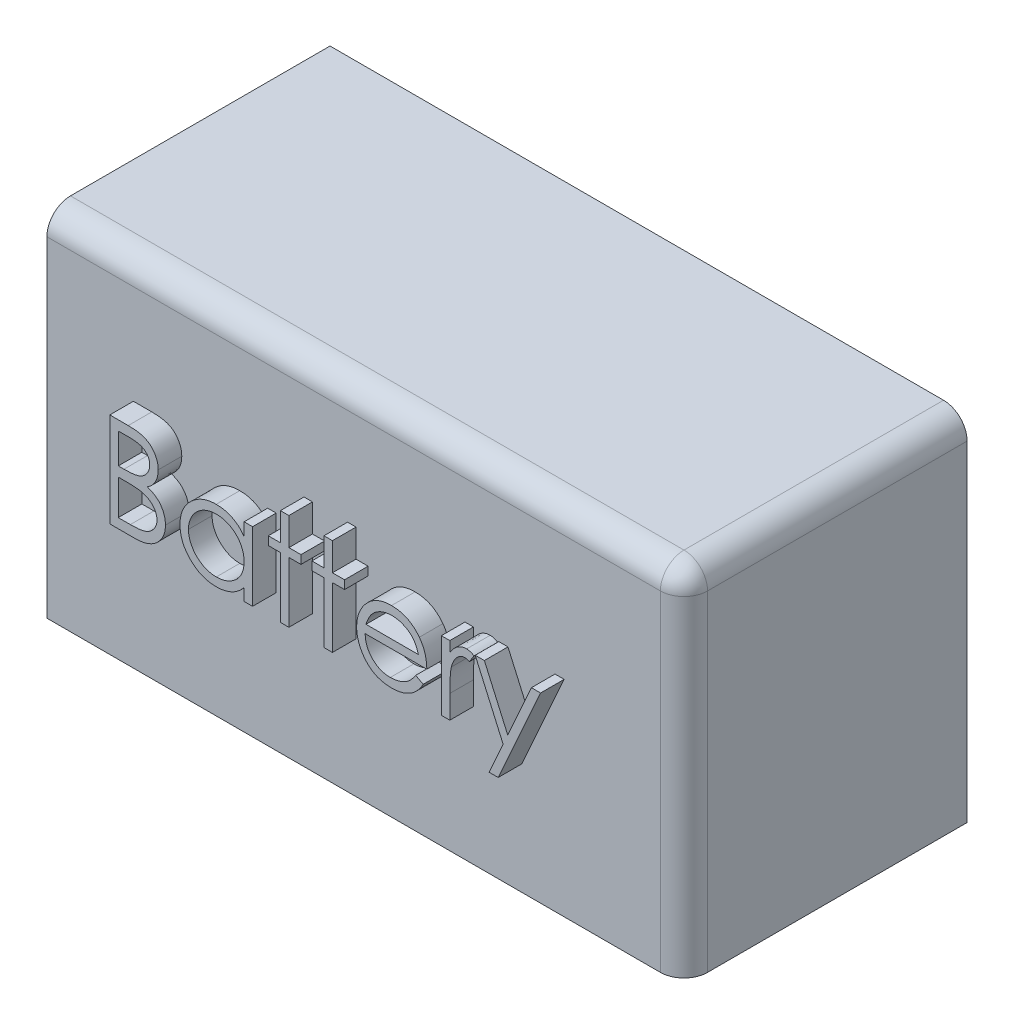
SolidWorks part; units mm, degrees
ref_plane "Front Plane" through (0, 0, 0) normal (0, 0, 1) x (1, 0, 0)
ref_plane "Top Plane" through (0, 0, 0) normal (0, 1, 0) x (1, 0, 0)
ref_plane "Right Plane" through (0, 0, 0) normal (1, 0, 0) x (0, 0, -1)
sketch "Sketch1" plane through (0, 0, 0) normal (0, 0, 1) x (1, 0, 0)
  line L1 (-67.5, -37.5) -> (67.5, -37.5)
  line L2 (-67.5, -37.5) -> (-67.5, 37.5)
  line L3 (-67.5, 37.5) -> (67.5, 37.5)
  line L4 (67.5, -37.5) -> (67.5, 37.5)
  line L5 (0, 37.5) -> (0, -37.5) construction
  line L6 (-67.5, 0) -> (67.5, 0) construction
  point P0 (0, 0)
  dimension "D1" = 135
  dimension "D2" = 75
extrude "Boss-Extrude1" add sketch "Sketch1" along normal blind 60
fillet "Fillet2" radius 5 3 edges at (67.5, 0, 60) (67.5, 37.5, 30) (0, 37.5, 60)
sketch "Sketch2" plane through (0, 0, 60) normal (0, 0, 1) x (1, 0, 0)
  text T0 "Battery" font "Century Gothic" height 20
extrude "Boss-Extrude2" add sketch "Sketch2" along normal blind 5
